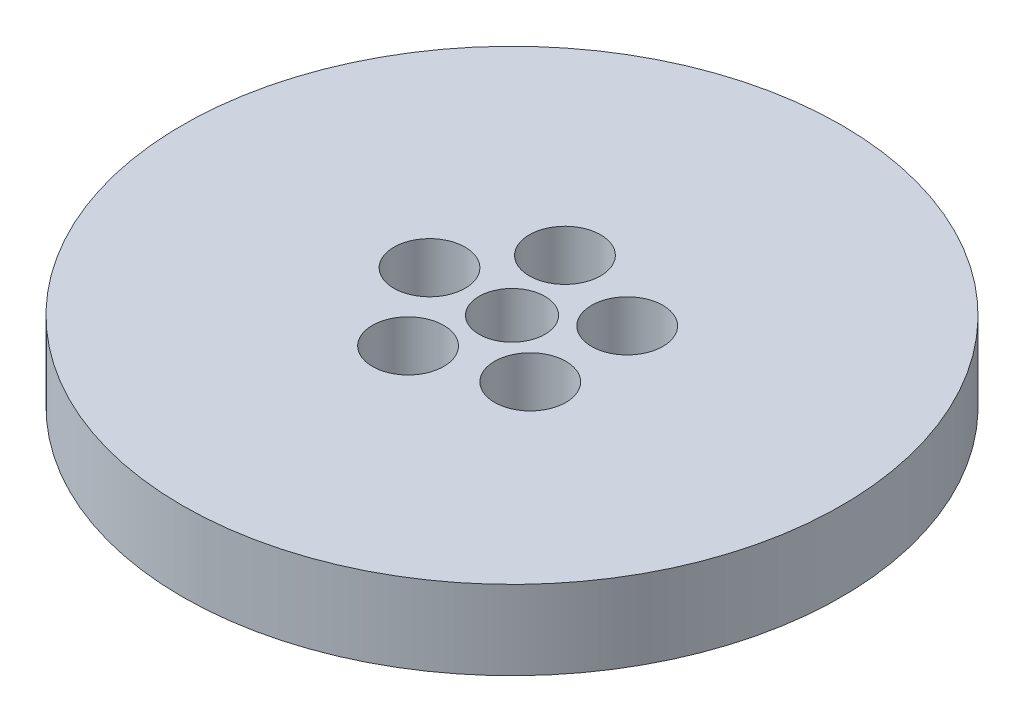
SolidWorks part; units mm, degrees
ref_plane "Front Plane" through (0, 0, 0) normal (0, 0, 1) x (1, 0, 0)
ref_plane "Top Plane" through (0, 0, 0) normal (0, 1, 0) x (1, 0, 0)
ref_plane "Right Plane" through (0, 0, 0) normal (1, 0, 0) x (0, 0, -1)
sketch "Sketch1" plane through (0, 0, 0) normal (0, 1, 0) x (1, 0, 0)
  circle A0 centre (0, 0) radius 50
  dimension "FLANGE_OD" = 100
extrude "Boss-Extrude1" add sketch "Sketch1" along normal blind 12
sketch "Sketch2" plane through (0, 0, 0) normal (0, 1, 0) x (1, 0, 0)
  circle A0 centre (0, 0) radius 5
  dimension "BORE_D" = 10
extrude "Cut-Extrude1" cut sketch "Sketch2" along normal through all
sketch "Sketch3" plane through (0, 12, 0) normal (0, 1, 0) x (1, 0, 0)
  circle A0 centre (0, 0) radius 12.5139 construction
  circle A1 centre (-12.5139, 0) radius 5.4101
  dimension "BOLT_D" = 10.8201
  dimension "BOLT_PCD" = 25.0279
extrude "Cut-Extrude2" cut sketch "Sketch3" against normal blind 11.7991
pattern_circular "CirPattern1" count 5 over 360 about axis through (0, 0, 0) along (0, 1, 0) of "Cut-Extrude2"
